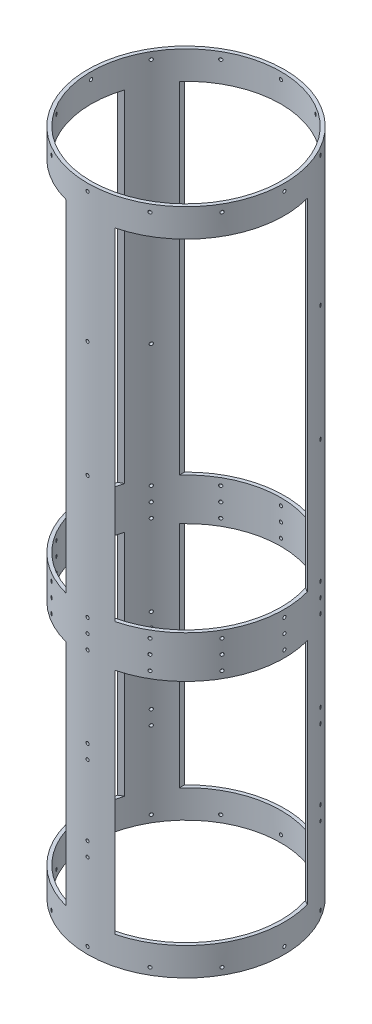
SolidWorks part; units mm, degrees
material "6061-T6 (SS)"
ref_plane "Front Plane" through (0, 0, 0) normal (0, 0, 1) x (1, 0, 0)
ref_plane "Top Plane" through (0, 0, 0) normal (0, 1, 0) x (1, 0, 0)
ref_plane "Right Plane" through (0, 0, 0) normal (1, 0, 0) x (0, 0, -1)
sketch "Sketch1" plane through (0, 0, 0) normal (0, 1, 0) x (1, 0, 0)
  circle A0 centre (0, 0) radius 88.9
  circle A1 centre (0, 0) radius 85.725
  dimension "D1" = 177.8
  dimension "D2" = 171.45
extrude "Boss-Extrude1" add sketch "Sketch1" along normal mid plane 603.25
sketch "Sketch2" plane through (0, 0, 0) normal (0, 0, 1) x (1, 0, 0)
  line L0 (88.9, -301.625) -> (88.9, 301.625) construction
  line L5 (-88.9, -301.625) -> (88.9, -301.625) construction
  line L6 (63.5, -276.225) -> (-63.5, -276.225)
  line L7 (-88.9, 301.625) -> (-88.9, -301.625) construction
  line L9 (63.5, -276.225) -> (63.5, -69.723)
  line L10 (63.5, -69.723) -> (-63.5, -69.723)
  line L11 (-63.5, -276.225) -> (-63.5, -69.723)
  line L12 (85.725, 301.625) -> (-85.725, 301.625) construction
  line L13 (63.5, -31.623) -> (-63.5, -31.623)
  line L14 (63.5, -31.623) -> (63.5, 276.225)
  line L15 (63.5, 276.225) -> (-63.5, 276.225)
  line L16 (-63.5, -31.623) -> (-63.5, 276.225)
  dimension "D1" = 25.4
  dimension "D2" = 25.4
  dimension "D3" = 25.4
  dimension "D4" = 231.902
  dimension "D5" = 25.4
  dimension "D6" = 38.1
extrude "Cut-Extrude1" cut sketch "Sketch2" against normal up to surface (62.217 mm away) up to face at (0, 301.625, 88.9)
pattern_circular "CirPattern1" count 3 over 360 about axis through (0, 301.625, 0) along (0, -1, 0) of "Cut-Extrude1"
ref_plane "Plane1" through (0, 0, 88.9) normal (0, 0, 1) x (1, 0, 0)
sketch "Sketch3" plane through (0, 0, 88.9) normal (0, 0, 1) x (1, 0, 0)
  line L0 (0, -97.79) -> (0, 97.79) construction
  line L1 (88.9, 301.625) -> (-88.9, 301.625) construction
  circle A0 centre (0, 295.275) radius 1.4351
  dimension "D1" = 2.8702
  dimension "D2" = 6.35
extrude "Cut-Extrude2" cut sketch "Sketch3" against normal blind 25.908
pattern_circular "CirPattern2" count 12 over 360 about axis through (0, 301.625, 0) along (0, -1, 0) of "Cut-Extrude2"
mirror "Mirror1" about plane through (0, 0, 0) normal (0, 1, 0) of "CirPattern2"
sketch "Sketch4" plane through (0, 0, 88.9) normal (0, 0, 1) x (1, 0, 0)
  line L0 (0, -97.79) -> (0, 97.79) construction
  circle A0 centre (0, -225.425) radius 1.4351
  circle A1 centre (0, -212.725) radius 1.4351
  circle A2 centre (0, -295.275) radius 1.4351 construction
  circle A3 centre (0, -149.225) radius 1.4351
  circle A4 centre (0, -136.525) radius 1.4351
  dimension "D1" = 69.85
  dimension "D2" = 2.8702
  dimension "D3" = 12.7
  dimension "D4" = 2.8702
  dimension "D5" = 63.5
  dimension "D6" = 12.7
  dimension "D7" = 2.8702
  dimension "D8" = 2.8702
extrude "Cut-Extrude3" cut sketch "Sketch4" against normal blind 34.798
pattern_circular "CirPattern3" count 3 over 360 about axis through (0, 301.625, 0) along (0, -1, 0) of "Cut-Extrude3" reverse direction yes
sketch "Sketch5" plane through (0, 0, 88.9) normal (0, 0, 1) x (1, 0, 0)
  line L0 (0, -97.79) -> (0, 97.79) construction
  line L1 (-22.1315, -31.623) -> (-88.9, -31.623) construction
  line L2 (-88.9, -69.723) -> (-22.1315, -69.723) construction
  line L3 (88.9, -31.623) -> (22.1315, -31.623) construction
  circle A0 centre (0, -50.673) radius 1.4351
  circle A1 centre (0, 73.025) radius 1.4351
  circle A2 centre (0, 177.927) radius 1.4351
  circle A3 centre (0, 295.275) radius 1.4351 construction
  circle A4 centre (0, -37.973) radius 1.4351
  circle A5 centre (0, -63.373) radius 1.4351
  dimension "D1" = 2.8702
  dimension "D3" = 117.348
  dimension "D5" = 2.8702
  dimension "D6" = 2.8702
  dimension "D4" = 123.698
  dimension "D7" = 2.8702
  dimension "D8" = 2.8702
  dimension "D9" = 6.35
  dimension "D10" = 6.35
  dimension "D2" = 19.05
extrude "Cut-Extrude4" cut sketch "Sketch5" against normal blind 87.63
pattern_circular "CirPattern4" count 12 over 360 about axis through (0, 301.625, 0) along (0, -1, 0) of "Cut-Extrude4" reverse direction yes
